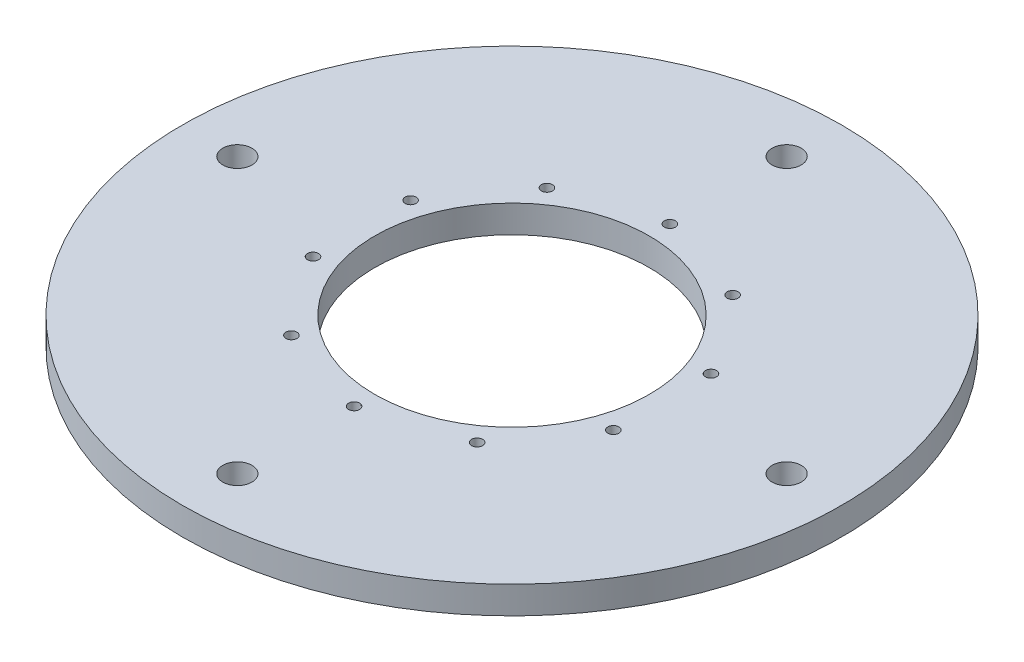
SolidWorks part; units mm, degrees
material "6061 Alloy"
ref_plane "Front Plane" through (0, 0, 0) normal (0, 0, 1) x (1, 0, 0)
ref_plane "Top Plane" through (0, 0, 0) normal (0, 1, 0) x (1, 0, 0)
ref_plane "Right Plane" through (0, 0, 0) normal (1, 0, 0) x (0, 0, -1)
sketch "Sketch1" plane through (0, 0, 0) normal (0, 1, 0) x (1, 0, 0)
  circle A3 centre (0, 0) radius 152.4
  circle A8 centre (0, 0) radius 127 construction
  circle A20 centre (0, 0) radius 63.5
  circle A23 centre (0, 0) radius 73.025 construction
  point P2 (0, 127)
  point P5 (0, 73.025)
  dimension "Diameter_Takeout_BoltCircle" = 254
  dimension "Diameter_ThrustPlate" = 304.8
  dimension "D2" = 146.05
  dimension "D4" = 127
extrude "ThrustPlate_TC3" add sketch "Sketch1" against normal blind 12.7 separate body contours A3 region at (-148.0895, 0, 0)
sketch "Sketch11" plane through (0, 0, 0) normal (0, 1, 0) x (1, 0, 0)
  point P0 (0, 127)
hole_wizard "UNDEF_Clearance_ThrustPlate" positions "Sketch11" profile "Sketch12" hole size "1/2" standard "ANSI Inch" end condition through all
sketch "Sketch12" plane through (0, 0, -127) normal (1, 0, 0) x (0, 0, 1)
  line L0 (0, 0) -> (0, 12.7)
  line L1 (0, 12.7) -> (6.7462, 12.7)
  line L2 (6.7462, 12.7) -> (6.7462, 0)
  line L5 (6.7462, 0) -> (0, 0)
  line L11 (0, -6.35) -> (0, 107.95) construction
  dimension "Thru Hole Dia." = 13.4925
  dimension "Thru Hole Depth" = 12.7
pattern_circular "Clearance_ThrustPlate_Pattern" count 4 over 360 about axis through (0, -12.7, 0) along (0, 1, 0) of "UNDEF_Clearance_ThrustPlate" reverse direction yes
sketch "Sketch22" plane through (0, 0, 0) normal (0, 1, 0) x (1, 0, 0)
  point P0 (0, 73.025)
hole_wizard "#10 Clearance Hole1" positions "Sketch22" profile "Sketch23" hole size "#10" standard "ANSI Inch" end condition through all
sketch "Sketch23" plane through (0, 0, -73.025) normal (1, 0, 0) x (0, 0, 1)
  line L0 (0, 0) -> (0, 12.7)
  line L1 (0, 12.7) -> (2.5527, 12.7)
  line L2 (2.5527, 12.7) -> (2.5527, 0)
  line L5 (2.5527, 0) -> (0, 0)
  line L11 (0, -6.35) -> (0, 107.95) construction
  dimension "Thru Hole Dia." = 5.1054
  dimension "Thru Hole Depth" = 12.7
pattern_circular "CirPattern1" count 10 over 360 about axis through (0, -12.7, 0) along (0, 1, 0) of "#10 Clearance Hole1" reverse direction yes
equation "\"Diameter_BackPlate\" = 6"
equation "\"VAR_Diameter_BackPlate_BoltCircle\" = 5.75"
equation "\"VAR_Diameter_FuelOuterPlenum\"= 4.4"
equation "\"Thickness_ThrustPlate\"= 0.5'undetermined"
equation "\"Diameter_ThrustPlate\"= 12'defined"
equation "\"Diameter_Takeout_BoltCicle\"= 10'defined"
equation "\"Diameter_Takeout_BoltCircle@Sketch1\"=\"Diameter_Takeout_BoltCicle\""
equation "\"Diameter_ThrustPlate@Sketch1\"=\"Diameter_ThrustPlate\""
equation "\"D1@ThrustPlate_TC3\"=\"Thickness_ThrustPlate\""
equation "\"VAR_Diameter_CBORE\"= 0.44'undetermined"
equation "\"VAR_Diameter_Clearance_ThrustPlate\"= 0.25'undetermined"
equation "\"NumberBolts_BackPlate\"= 20"
equation "\"NumberBolts_Takeout\"= 4'defined"
equation "\"D1@Clearance_ThrustPlate_Pattern\"=\"NumberBolts_Takeout\""
